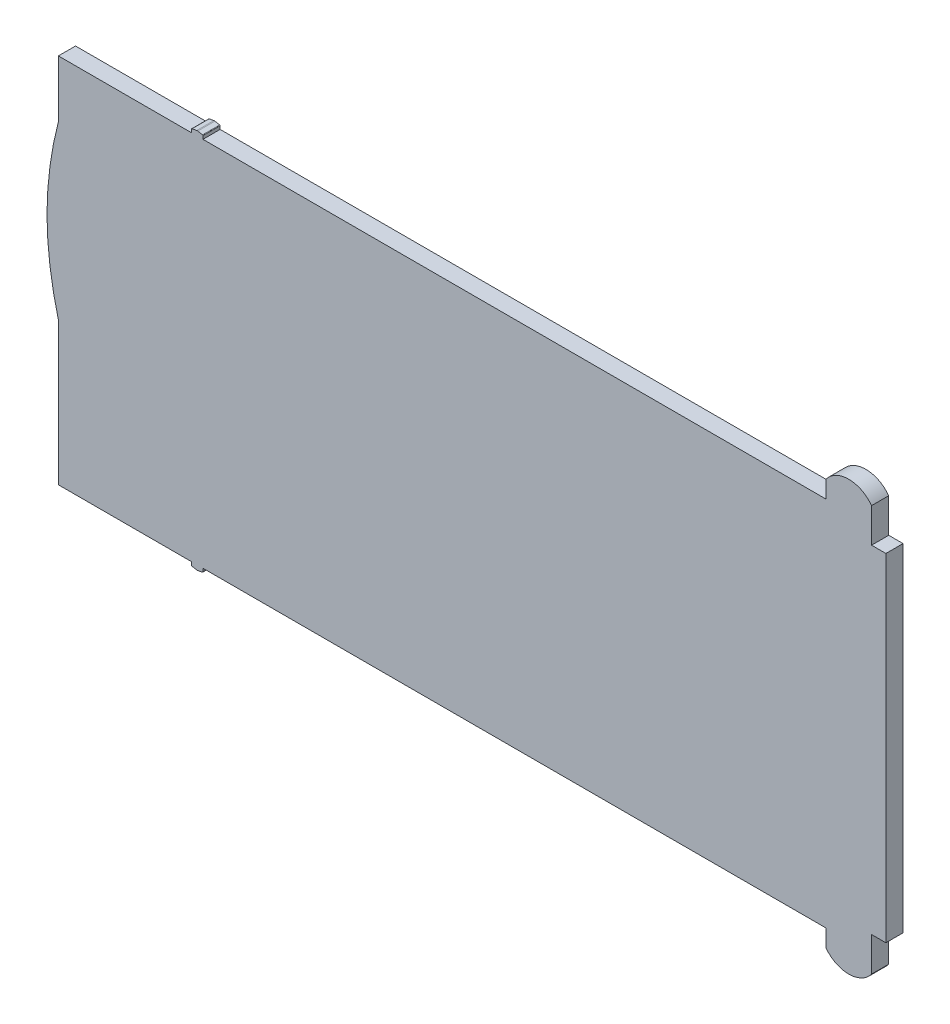
SolidWorks part; units mm, degrees
material "Vidrio"
ref_plane "Alzado" through (0, 0, 0) normal (0, 0, 1) x (1, 0, 0)
ref_plane "Planta" through (0, 0, 0) normal (0, 1, 0) x (1, 0, 0)
ref_plane "Vista lateral" through (0, 0, 0) normal (1, 0, 0) x (0, 0, -1)
sketch "Croquis1" plane through (0, 0, 0) normal (0, 0, 1) x (1, 0, 0)
  line L0 (23.1977, 55.1953) -> (17.6238, 55.1517)
  line L1 (17.6238, 55.1517) -> (19.2257, 49.2985)
  line L2 (21.9668, 38.9626) -> (21.0109, 39.0194)
  line L3 (21.0109, 39.0194) -> (18.7543, 47.2339)
  line L4 (35.1267, 52.7205) -> (35.7465, 50.9877)
  line L5 (35.7465, 50.9877) -> (33.2105, 49.6869)
  line L6 (27.676, 46.9939) -> (26.707, 46.4745)
  line L7 (26.707, 46.4745) -> (27.0387, 46.1034)
  line L8 (29.3302, 43.6068) -> (31.2289, 41.5466)
  line L9 (31.2289, 41.5466) -> (32.0146, 39.1983)
  line L10 (30.4913, 38.7484) -> (28.3743, 40.857)
  line L11 (28.3743, 40.857) -> (27.7982, 40.5165)
  line L12 (27.7982, 40.5165) -> (27.0867, 40.0975)
  line L13 (27.0867, 40.0975) -> (26.4626, 41.1014)
  line L14 (24.817, 43.7639) -> (23.7302, 45.5273)
  line L15 (23.7302, 45.5273) -> (24.0576, 47.2514)
  line L16 (33.6427, 44.4885) -> (31.2158, 42.7862)
  line L17 (31.2158, 42.7862) -> (29.5397, 44.4448)
  line L18 (155.5622, 17.217) -> (155.5622, 76.2168)
  line L19 (153.0622, 82.2168) -> (153.0622, 79.2168)
  line L20 (145.0622, 82.2168) -> (145.0622, 79.2168)
  line L21 (145.0622, 11.217) -> (145.0622, 14.217)
  line L22 (153.0622, 11.217) -> (153.0622, 14.217)
  line L23 (34.0621, 79.2168) -> (10.0621, 79.2168)
  line L24 (10.0621, 14.217) -> (10.0621, 79.2168)
  line L25 (10.0621, 79.2168) -> (34.0621, 79.2168)
  line L27 (145.0622, 79.2168) -> (36.0621, 79.2252)
  line L28 (10.0621, 14.217) -> (34.0437, 14.217)
  line L29 (36.0437, 14.2253) -> (145.0622, 14.217)
  line L30 (34.1437, 79.8689) -> (34.97, 80.0238)
  line L31 (35.9805, 79.8689) -> (35.1543, 80.0238)
  line L32 (35.9621, 13.5732) -> (35.1358, 13.4183)
  line L33 (34.1253, 13.5732) -> (34.9515, 13.4183)
  line L34 (153.0622, 14.217) -> (153.0622, 17.217)
  line L35 (153.0622, 17.217) -> (155.5622, 17.217)
  line L36 (153.0622, 79.2168) -> (153.0622, 76.2168)
  line L37 (153.0622, 76.2168) -> (155.5622, 76.2168)
  line L38 (36.0621, 79.2252) -> (36.0621, 79.7706)
  line L39 (34.0621, 79.7706) -> (34.0621, 79.2168)
  line L40 (34.0437, 14.217) -> (34.0437, 13.6715)
  line L41 (36.0437, 13.6715) -> (36.0437, 14.2253)
  arc A1 (34.1437, 79.8689) -> (34.0621, 79.7706) centre (34.1621, 79.7706) ccw
  arc A2 (36.0621, 79.7706) -> (35.9805, 79.8689) centre (35.9621, 79.7706) ccw
  arc A3 (35.9621, 13.5732) -> (36.0437, 13.6715) centre (35.9437, 13.6715) ccw
  arc A4 (34.0437, 13.6715) -> (34.1253, 13.5732) centre (34.1437, 13.6715) ccw
  arc A5 (35.1543, 80.0238) -> (34.97, 80.0238) centre (35.0621, 79.5324) ccw
  arc A6 (34.9515, 13.4183) -> (35.1358, 13.4183) centre (35.0437, 13.9097) ccw
  arc A7 (153.0622, 82.2168) -> (145.0622, 82.2168) centre (149.0622, 79.2165) ccw
  arc A8 (145.0622, 11.217) -> (153.0622, 11.217) centre (149.0622, 14.217) ccw
  spline S0 degree 3 poles (22.9882, 56.2909) (24.465, 56.2802) (25.9512, 56.2546) (27.1129, 56.2211) knots 0 0 0 0 1 1 1 1
  spline S1 degree 3 poles (27.1129, 56.2211) (27.6938, 56.2043) (28.1916, 56.1859) (28.5708, 56.1643) knots 0 0 0 0 1 1 1 1
  spline S2 degree 3 poles (28.5708, 56.1643) (28.9499, 56.1427) (29.1978, 56.1233) (29.3171, 56.0901) knots 0 0 0 0 1 1 1 1
  spline S3 degree 3 poles (29.3171, 56.0901) (30.1079, 55.8706) (30.8888, 55.1338) (31.4122, 54.318) knots 0 0 0 0 1 1 1 1
  spline S4 degree 3 poles (31.4122, 54.318) (31.674, 53.9101) (31.8707, 53.4822) (31.9666, 53.0828) knots 0 0 0 0 1 1 1 1
  spline S5 degree 3 poles (31.9666, 53.0828) (32.0625, 52.6834) (32.0614, 52.3092) (31.9055, 52.0178) knots 0 0 0 0 1 1 1 1
  spline S6 degree 3 poles (31.9055, 52.0178) (31.8337, 51.8836) (31.7742, 51.787) (31.696, 51.7253) knots 0 0 0 0 1 1 1 1
  spline S7 degree 3 poles (31.696, 51.7253) (31.6568, 51.6945) (31.6061, 51.6722) (31.5519, 51.6773) knots 0 0 0 0 1 1 1 1
  spline S8 degree 3 poles (31.5519, 51.6773) (31.4977, 51.6824) (31.449, 51.7134) (31.4122, 51.7515) knots 0 0 0 0 1 1 1 1
  spline S9 degree 3 poles (31.4122, 51.7515) (31.3388, 51.8278) (31.2827, 51.9445) (31.2115, 52.1225) knots 0 0 0 0 1 1 1 1
  spline S10 degree 3 poles (31.2115, 52.1225) (31.1403, 52.3005) (31.0608, 52.5367) (30.9627, 52.8427) knots 0 0 0 0 1 1 1 1
  spline S11 degree 3 poles (30.9627, 52.8427) (30.5664, 54.0785) (30.176, 54.6186) (29.4481, 54.964) knots 0 0 0 0 1 1 1 1
  spline S12 degree 3 poles (29.4481, 54.964) (29.198, 55.0826) (28.8811, 55.1528) (27.999, 55.1866) knots 0 0 0 0 1 1 1 1
  spline S13 degree 3 poles (27.999, 55.1866) (27.1169, 55.2204) (25.6803, 55.2155) (23.1977, 55.1953) knots 0 0 0 0 1 1 1 1
  spline S14 degree 3 poles (19.2257, 49.2985) (20.1234, 46.0188) (21.0684, 42.5658) (21.3252, 41.6252) knots 0 0 0 0 1 1 1 1
  spline S15 degree 3 poles (21.3252, 41.6252) (21.5575, 40.7742) (21.6788, 40.3445) (21.7922, 40.1542) knots 0 0 0 0 1 1 1 1
  spline S16 degree 3 poles (21.7922, 40.1542) (21.8489, 40.0591) (21.8933, 40.0262) (21.9581, 40.0058) knots 0 0 0 0 1 1 1 1
  spline S17 degree 3 poles (21.9581, 40.0058) (22.0229, 39.9855) (22.1186, 39.9826) (22.2549, 39.984) knots 0 0 0 0 1 1 1 1
  spline S18 degree 3 poles (22.2549, 39.984) (22.5346, 39.9868) (22.9349, 40.1132) (23.0929, 40.2328) knots 0 0 0 0 1 1 1 1
  spline S19 degree 3 poles (23.0929, 40.2328) (23.567, 40.5914) (24.1358, 40.577) (24.5595, 40.1935) knots 0 0 0 0 1 1 1 1
  spline S20 degree 3 poles (24.5595, 40.1935) (24.9472, 39.8426) (25.0001, 39.3177) (24.7166, 38.788) knots 0 0 0 0 1 1 1 1
  spline S21 degree 3 poles (24.7166, 38.788) (24.5805, 38.5338) (24.2425, 38.4181) (23.9004, 38.3996) knots 0 0 0 0 1 1 1 1
  spline S22 degree 3 poles (23.9004, 38.3996) (23.5584, 38.381) (23.1997, 38.4591) (23.01, 38.6877) knots 0 0 0 0 1 1 1 1
  spline S23 degree 3 poles (23.01, 38.6877) (22.9777, 38.7266) (22.8378, 38.8007) (22.6477, 38.8535) knots 0 0 0 0 1 1 1 1
  spline S24 degree 3 poles (22.6477, 38.8535) (22.4576, 38.9063) (22.2156, 38.948) (21.9668, 38.9626) knots 0 0 0 0 1 1 1 1
  spline S25 degree 3 poles (18.7543, 47.2339) (18.1386, 49.4769) (17.5776, 51.5477) (17.1699, 53.0784) knots 0 0 0 0 1 1 1 1
  spline S26 degree 3 poles (17.1699, 53.0784) (16.966, 53.8438) (16.8004, 54.4756) (16.6854, 54.9247) knots 0 0 0 0 1 1 1 1
  spline S27 degree 3 poles (16.6854, 54.9247) (16.6279, 55.1493) (16.5809, 55.3286) (16.5501, 55.4572) knots 0 0 0 0 1 1 1 1
  spline S28 degree 3 poles (16.5501, 55.4572) (16.5347, 55.5216) (16.5235, 55.5711) (16.5152, 55.61) knots 0 0 0 0 1 1 1 1
  spline S29 degree 3 poles (16.5152, 55.61) (16.5069, 55.6489) (16.5032, 55.6672) (16.5021, 55.6973) knots 0 0 0 0 1 1 1 1
  spline S30 degree 3 poles (16.5021, 55.6973) (16.4949, 55.9024) (16.6315, 56.1032) (16.8251, 56.1774) knots 0 0 0 0 1 1 1 1
  spline S31 degree 3 poles (16.8251, 56.1774) (16.8825, 56.1995) (16.9526, 56.2063) (17.0651, 56.2167) knots 0 0 0 0 1 1 1 1
  spline S32 degree 3 poles (17.0651, 56.2167) (17.1777, 56.2271) (17.3227, 56.2391) (17.5016, 56.2473) knots 0 0 0 0 1 1 1 1
  spline S33 degree 3 poles (17.5016, 56.2473) (17.8595, 56.2636) (18.3449, 56.2737) (18.9115, 56.2822) knots 0 0 0 0 1 1 1 1
  spline S34 degree 3 poles (18.9115, 56.2822) (20.0446, 56.2991) (21.5114, 56.3016) (22.9882, 56.2909) knots 0 0 0 0 1 1 1 1
  spline S35 degree 3 poles (34.4109, 54.4926) (34.4112, 54.4925) (34.4543, 54.471) (34.4545, 54.4708) knots 0 0 0 0 1 1 1 1
  spline S36 degree 3 poles (34.4545, 54.4708) (34.455, 54.4703) (34.4652, 54.461) (34.4676, 54.4577) knots 0 0 0 0 1 1 1 1
  spline S37 degree 3 poles (34.4676, 54.4577) (34.47, 54.4544) (34.4704, 54.4515) (34.472, 54.4489) knots 0 0 0 0 1 1 1 1
  spline S38 degree 3 poles (34.472, 54.4489) (34.4751, 54.4438) (34.4782, 54.4365) (34.4807, 54.4315) knots 0 0 0 0 1 1 1 1
  spline S39 degree 3 poles (34.4807, 54.4315) (34.4858, 54.4216) (34.4921, 54.4103) (34.4982, 54.3966) knots 0 0 0 0 1 1 1 1
  spline S40 degree 3 poles (34.4982, 54.3966) (34.5104, 54.3691) (34.5232, 54.3334) (34.5418, 54.2875) knots 0 0 0 0 1 1 1 1
  spline S41 degree 3 poles (34.5418, 54.2875) (34.5789, 54.1955) (34.6312, 54.0679) (34.6902, 53.9121) knots 0 0 0 0 1 1 1 1
  spline S42 degree 3 poles (34.6902, 53.9121) (34.8083, 53.6004) (34.9626, 53.1779) (35.1267, 52.7205) knots 0 0 0 0 1 1 1 1
  spline S43 degree 3 poles (33.2105, 49.6869) (32.5306, 49.3396) (31.8967, 49.0229) (31.4253, 48.7922) knots 0 0 0 0 1 1 1 1
  spline S44 degree 3 poles (31.4253, 48.7922) (31.1897, 48.6768) (30.9951, 48.5828) (30.8536, 48.5172) knots 0 0 0 0 1 1 1 1
  spline S45 degree 3 poles (30.8536, 48.5172) (30.7828, 48.4843) (30.7262, 48.4611) (30.6833, 48.443) knots 0 0 0 0 1 1 1 1
  spline S46 degree 3 poles (30.6833, 48.443) (30.6619, 48.4339) (30.6416, 48.4267) (30.6266, 48.4211) knots 0 0 0 0 1 1 1 1
  spline S47 degree 3 poles (30.6266, 48.4211) (30.6191, 48.4184) (30.6119, 48.4145) (30.6047, 48.4124) knots 0 0 0 0 1 1 1 1
  spline S48 degree 3 poles (30.6047, 48.4124) (30.5976, 48.4103) (30.5807, 48.4082) (30.5786, 48.408) knots 0 0 0 0 1 1 1 1
  spline S49 degree 3 poles (30.5786, 48.408) (30.578, 48.408) (30.5484, 48.4123) (30.548, 48.4124) knots 0 0 0 0 1 1 1 1
  spline S50 degree 3 poles (30.548, 48.4124) (30.5476, 48.4125) (30.5134, 48.4296) (30.5131, 48.4299) knots 0 0 0 0 1 1 1 1
  spline S51 degree 3 poles (30.5131, 48.4299) (30.5128, 48.4301) (30.4915, 48.46) (30.4913, 48.4604) knots 0 0 0 0 1 1 1 1
  spline S52 degree 3 poles (30.4913, 48.4604) (30.491, 48.4609) (30.4826, 48.4816) (30.4825, 48.4822) knots 0 0 0 0 1 1 1 1
  spline S53 degree 3 poles (30.4825, 48.4822) (30.4824, 48.4828) (30.4782, 48.4989) (30.4782, 48.4997) knots 0 0 0 0 1 1 1 1
  spline S54 degree 3 poles (30.4782, 48.4997) (30.4782, 48.5005) (30.4821, 48.5091) (30.4825, 48.5128) knots 0 0 0 0 1 1 1 1
  spline S55 degree 3 poles (30.4825, 48.5128) (30.4833, 48.5201) (30.4812, 48.525) (30.4825, 48.5302) knots 0 0 0 0 1 1 1 1
  spline S56 degree 3 poles (30.4825, 48.5302) (30.4877, 48.5514) (30.4944, 48.5694) (30.5043, 48.5913) knots 0 0 0 0 1 1 1 1
  spline S57 degree 3 poles (30.5043, 48.5913) (30.5243, 48.6352) (30.5579, 48.694) (30.6004, 48.7703) knots 0 0 0 0 1 1 1 1
  spline S58 degree 3 poles (30.6004, 48.7703) (30.6854, 48.923) (30.8147, 49.1415) (30.9801, 49.412) knots 0 0 0 0 1 1 1 1
  spline S59 degree 3 poles (30.9801, 49.412) (31.3109, 49.9529) (31.7843, 50.6981) (32.3201, 51.5202) knots 0 0 0 0 1 1 1 1
  spline S60 degree 3 poles (32.3201, 51.5202) (32.8559, 52.3421) (33.3493, 53.0828) (33.7125, 53.6153) knots 0 0 0 0 1 1 1 1
  spline S61 degree 3 poles (33.7125, 53.6153) (33.8941, 53.8815) (34.0427, 54.0973) (34.149, 54.2438) knots 0 0 0 0 1 1 1 1
  spline S62 degree 3 poles (34.149, 54.2438) (34.2021, 54.3171) (34.244, 54.3708) (34.2756, 54.4097) knots 0 0 0 0 1 1 1 1
  spline S63 degree 3 poles (34.2756, 54.4097) (34.2913, 54.4291) (34.3019, 54.4448) (34.3148, 54.4577) knots 0 0 0 0 1 1 1 1
  spline S64 degree 3 poles (34.3148, 54.4577) (34.3213, 54.4641) (34.3284, 54.4714) (34.341, 54.4795) knots 0 0 0 0 1 1 1 1
  spline S65 degree 3 poles (34.341, 54.4795) (34.3442, 54.4815) (34.3536, 54.4836) (34.3541, 54.4839) knots 0 0 0 0 1 1 1 1
  spline S66 degree 3 poles (34.3541, 54.4839) (34.3547, 54.4841) (34.3711, 54.4925) (34.3716, 54.4926) knots 0 0 0 0 1 1 1 1
  spline S67 degree 3 poles (34.3716, 54.4926) (34.372, 54.4927) (34.4105, 54.4927) (34.4109, 54.4926) knots 0 0 0 0 1 1 1 1
  spline S68 degree 3 poles (20.2078, 53.445) (20.241, 53.4449) (20.2808, 53.4417) (20.33, 53.4363) knots 0 0 0 0 1 1 1 1
  spline S69 degree 3 poles (20.33, 53.4363) (20.4284, 53.4256) (20.562, 53.4079) (20.7228, 53.3796) knots 0 0 0 0 1 1 1 1
  spline S70 degree 3 poles (20.7228, 53.3796) (21.0446, 53.3229) (21.4762, 53.2337) (21.9406, 53.1264) knots 0 0 0 0 1 1 1 1
  spline S71 degree 3 poles (21.9406, 53.1264) (22.7572, 52.9377) (23.1816, 52.8405) (23.5076, 52.8296) knots 0 0 0 0 1 1 1 1
  spline S72 degree 3 poles (23.5076, 52.8296) (23.8336, 52.8187) (24.0705, 52.8892) (24.5333, 53.0348) knots 0 0 0 0 1 1 1 1
  spline S73 degree 3 poles (24.5333, 53.0348) (25.5486, 53.3541) (26.2772, 53.3011) (27.1827, 52.8383) knots 0 0 0 0 1 1 1 1
  spline S74 degree 3 poles (27.1827, 52.8383) (27.5743, 52.6383) (27.8631, 52.3158) (28.0601, 51.8301) knots 0 0 0 0 1 1 1 1
  spline S75 degree 3 poles (28.0601, 51.8301) (28.257, 51.3443) (28.3695, 50.6957) (28.4311, 49.8092) knots 0 0 0 0 1 1 1 1
  spline S76 degree 3 poles (28.4311, 49.8092) (28.4611, 49.3767) (28.502, 48.9498) (28.5446, 48.6132) knots 0 0 0 0 1 1 1 1
  spline S77 degree 3 poles (28.5446, 48.6132) (28.5658, 48.4449) (28.5854, 48.2979) (28.6057, 48.1855) knots 0 0 0 0 1 1 1 1
  spline S78 degree 3 poles (28.6057, 48.1855) (28.626, 48.073) (28.6487, 47.9887) (28.6581, 47.9672) knots 0 0 0 0 1 1 1 1
  spline S79 degree 3 poles (28.6581, 47.9672) (28.689, 47.8962) (28.7008, 47.8176) (28.6755, 47.7402) knots 0 0 0 0 1 1 1 1
  spline S80 degree 3 poles (28.6755, 47.7402) (28.6503, 47.6629) (28.5967, 47.5935) (28.5184, 47.522) knots 0 0 0 0 1 1 1 1
  spline S81 degree 3 poles (28.5184, 47.522) (28.3616, 47.3791) (28.0966, 47.2181) (27.676, 46.9939) knots 0 0 0 0 1 1 1 1
  spline S82 degree 3 poles (27.0387, 46.1034) (27.263, 45.855) (28.2947, 44.7315) (29.3302, 43.6068) knots 0 0 0 0 1 1 1 1
  spline S83 degree 3 poles (32.0146, 39.1983) (32.2298, 38.5567) (32.427, 37.9622) (32.5689, 37.5223) knots 0 0 0 0 1 1 1 1
  spline S84 degree 3 poles (32.5689, 37.5223) (32.6399, 37.3023) (32.6948, 37.12) (32.7348, 36.9898) knots 0 0 0 0 1 1 1 1
  spline S85 degree 3 poles (32.7348, 36.9898) (32.7548, 36.9247) (32.772, 36.8754) (32.7828, 36.837) knots 0 0 0 0 1 1 1 1
  spline S86 degree 3 poles (32.7828, 36.837) (32.7882, 36.8178) (32.7928, 36.8019) (32.7959, 36.789) knots 0 0 0 0 1 1 1 1
  spline S87 degree 3 poles (32.7959, 36.789) (32.7974, 36.7825) (32.7992, 36.7731) (32.8002, 36.7671) knots 0 0 0 0 1 1 1 1
  spline S88 degree 3 poles (32.8002, 36.7671) (32.8014, 36.7613) (32.8002, 36.7467) (32.8002, 36.7452) knots 0 0 0 0 1 1 1 1
  spline S89 degree 3 poles (32.8002, 36.7452) (32.8002, 36.7448) (32.796, 36.7105) (32.7959, 36.7102) knots 0 0 0 0 1 1 1 1
  spline S90 degree 3 poles (32.7959, 36.7102) (32.7958, 36.71) (32.7612, 36.6711) (32.761, 36.671) knots 0 0 0 0 1 1 1 1
  spline S91 degree 3 poles (32.761, 36.671) (32.7607, 36.6708) (32.722, 36.658) (32.7217, 36.6578) knots 0 0 0 0 1 1 1 1
  spline S92 degree 3 poles (32.7217, 36.6578) (32.7213, 36.6577) (32.7003, 36.6577) (32.6999, 36.6578) knots 0 0 0 0 1 1 1 1
  spline S93 degree 3 poles (32.6999, 36.6578) (32.6989, 36.6579) (32.6792, 36.6597) (32.6737, 36.662) knots 0 0 0 0 1 1 1 1
  spline S94 degree 3 poles (32.6737, 36.662) (32.6681, 36.6645) (32.6644, 36.6685) (32.6606, 36.6707) knots 0 0 0 0 1 1 1 1
  spline S95 degree 3 poles (32.6606, 36.6707) (32.6452, 36.6797) (32.6329, 36.6886) (32.6169, 36.7013) knots 0 0 0 0 1 1 1 1
  spline S96 degree 3 poles (32.6169, 36.7013) (32.585, 36.7265) (32.5415, 36.7649) (32.486, 36.8148) knots 0 0 0 0 1 1 1 1
  spline S97 degree 3 poles (32.486, 36.8148) (32.3748, 36.9145) (32.2153, 37.0638) (32.019, 37.2513) knots 0 0 0 0 1 1 1 1
  spline S98 degree 3 poles (32.019, 37.2513) (31.6263, 37.6262) (31.0864, 38.1547) (30.4913, 38.7484) knots 0 0 0 0 1 1 1 1
  spline S99 degree 3 poles (26.4626, 41.1014) (26.1453, 41.6137) (25.4049, 42.8113) (24.817, 43.7639) knots 0 0 0 0 1 1 1 1
  spline S100 degree 3 poles (24.0576, 47.2514) (24.2337, 48.1791) (24.4293, 49.4157) (24.4897, 49.9881) knots 0 0 0 0 1 1 1 1
  spline S101 degree 3 poles (24.4897, 49.9881) (24.5411, 50.4762) (24.5583, 50.7412) (24.5159, 50.9222) knots 0 0 0 0 1 1 1 1
  spline S102 degree 3 poles (24.5159, 50.9222) (24.4734, 51.1032) (24.373, 51.2182) (24.1579, 51.4329) knots 0 0 0 0 1 1 1 1
  spline S103 degree 3 poles (24.1579, 51.4329) (24.0335, 51.5571) (23.7396, 51.7414) (23.3417, 51.9348) knots 0 0 0 0 1 1 1 1
  spline S104 degree 3 poles (23.3417, 51.9348) (22.9439, 52.1283) (22.4427, 52.3353) (21.8882, 52.5328) knots 0 0 0 0 1 1 1 1
  spline S105 degree 3 poles (21.8882, 52.5328) (21.3815, 52.7134) (20.9305, 52.8878) (20.6094, 53.0217) knots 0 0 0 0 1 1 1 1
  spline S106 degree 3 poles (20.6094, 53.0217) (20.4488, 53.0886) (20.3174, 53.1429) (20.2296, 53.1875) knots 0 0 0 0 1 1 1 1
  spline S107 degree 3 poles (20.2296, 53.1875) (20.1857, 53.2098) (20.1559, 53.2296) (20.1292, 53.2486) knots 0 0 0 0 1 1 1 1
  spline S108 degree 3 poles (20.1292, 53.2486) (20.1159, 53.2581) (20.1043, 53.2645) (20.0899, 53.2836) knots 0 0 0 0 1 1 1 1
  spline S109 degree 3 poles (20.0899, 53.2836) (20.0864, 53.2883) (20.0774, 53.3043) (20.0769, 53.3054) knots 0 0 0 0 1 1 1 1
  spline S110 degree 3 poles (20.0769, 53.3054) (20.0763, 53.3065) (20.0682, 53.3306) (20.0681, 53.3316) knots 0 0 0 0 1 1 1 1
  spline S111 degree 3 poles (20.0681, 53.3316) (20.068, 53.3325) (20.0722, 53.3744) (20.0725, 53.3752) knots 0 0 0 0 1 1 1 1
  spline S112 degree 3 poles (20.0725, 53.3752) (20.0728, 53.376) (20.0936, 53.4095) (20.0943, 53.4101) knots 0 0 0 0 1 1 1 1
  spline S113 degree 3 poles (20.0943, 53.4101) (20.095, 53.4108) (20.1151, 53.427) (20.1161, 53.4276) knots 0 0 0 0 1 1 1 1
  spline S114 degree 3 poles (20.1161, 53.4276) (20.1172, 53.4282) (20.1285, 53.4345) (20.1336, 53.4363) knots 0 0 0 0 1 1 1 1
  spline S115 degree 3 poles (20.1336, 53.4363) (20.1439, 53.44) (20.1518, 53.4395) (20.1598, 53.4407) knots 0 0 0 0 1 1 1 1
  spline S116 degree 3 poles (20.1598, 53.4407) (20.1757, 53.4431) (20.1912, 53.4451) (20.2078, 53.445) knots 0 0 0 0 1 1 1 1
  spline S117 degree 3 poles (37.9158, 51.1492) (37.9167, 51.1491) (37.9413, 51.145) (37.942, 51.1448) knots 0 0 0 0 1 1 1 1
  spline S118 degree 3 poles (37.942, 51.1448) (37.9426, 51.1446) (37.9766, 51.1233) (37.9769, 51.123) knots 0 0 0 0 1 1 1 1
  spline S119 degree 3 poles (37.9769, 51.123) (37.9779, 51.122) (37.9935, 51.0983) (37.9944, 51.0968) knots 0 0 0 0 1 1 1 1
  spline S120 degree 3 poles (37.9944, 51.0968) (37.9952, 51.0953) (38.0011, 51.0857) (38.0031, 51.0793) knots 0 0 0 0 1 1 1 1
  spline S121 degree 3 poles (38.0031, 51.0793) (38.0072, 51.0666) (38.0109, 51.0548) (38.0118, 51.0444) knots 0 0 0 0 1 1 1 1
  spline S122 degree 3 poles (38.0118, 51.0444) (38.0136, 51.0237) (38.0098, 51.0053) (38.0075, 50.9833) knots 0 0 0 0 1 1 1 1
  spline S123 degree 3 poles (38.0075, 50.9833) (38.0029, 50.9393) (37.9963, 50.8823) (37.9813, 50.8174) knots 0 0 0 0 1 1 1 1
  spline S124 degree 3 poles (37.9813, 50.8174) (37.9512, 50.6878) (37.9013, 50.5168) (37.8373, 50.3111) knots 0 0 0 0 1 1 1 1
  spline S125 degree 3 poles (37.8373, 50.3111) (37.7093, 49.8998) (37.5207, 49.3604) (37.3222, 48.8184) knots 0 0 0 0 1 1 1 1
  spline S126 degree 3 poles (37.3222, 48.8184) (37.1237, 48.2763) (36.9132, 47.73) (36.733, 47.2994) knots 0 0 0 0 1 1 1 1
  spline S127 degree 3 poles (36.733, 47.2994) (36.6428, 47.0841) (36.5624, 46.8968) (36.4929, 46.7538) knots 0 0 0 0 1 1 1 1
  spline S128 degree 3 poles (36.4929, 46.7538) (36.4234, 46.6109) (36.3771, 46.5208) (36.3183, 46.4614) knots 0 0 0 0 1 1 1 1
  spline S129 degree 3 poles (36.3183, 46.4614) (36.2674, 46.4099) (36.1648, 46.3245) (36.0084, 46.2039) knots 0 0 0 0 1 1 1 1
  spline S130 degree 3 poles (36.0084, 46.2039) (35.852, 46.0832) (35.6434, 45.9321) (35.4017, 45.7543) knots 0 0 0 0 1 1 1 1
  spline S131 degree 3 poles (35.4017, 45.7543) (34.9184, 45.3986) (34.2943, 44.9458) (33.6427, 44.4885) knots 0 0 0 0 1 1 1 1
  spline S132 degree 3 poles (29.5397, 44.4448) (29.093, 44.8869) (28.6868, 45.2991) (28.3918, 45.6102) knots 0 0 0 0 1 1 1 1
  spline S133 degree 3 poles (28.3918, 45.6102) (28.2443, 45.7658) (28.1264, 45.8942) (28.0426, 45.99) knots 0 0 0 0 1 1 1 1
  spline S134 degree 3 poles (28.0426, 45.99) (28.0007, 46.0379) (27.966, 46.0767) (27.9422, 46.1078) knots 0 0 0 0 1 1 1 1
  spline S135 degree 3 poles (27.9422, 46.1078) (27.9303, 46.1234) (27.9199, 46.1381) (27.9117, 46.1515) knots 0 0 0 0 1 1 1 1
  spline S136 degree 3 poles (27.9117, 46.1515) (27.9075, 46.1582) (27.9068, 46.1645) (27.9029, 46.1733) knots 0 0 0 0 1 1 1 1
  spline S137 degree 3 poles (27.9029, 46.1733) (27.901, 46.1777) (27.8946, 46.1895) (27.8942, 46.1908) knots 0 0 0 0 1 1 1 1
  spline S138 degree 3 poles (27.8942, 46.1908) (27.8938, 46.192) (27.8898, 46.216) (27.8898, 46.2169) knots 0 0 0 0 1 1 1 1
  spline S139 degree 3 poles (27.8898, 46.2169) (27.8898, 46.2175) (27.8983, 46.2556) (27.8986, 46.2562) knots 0 0 0 0 1 1 1 1
  spline S140 degree 3 poles (27.8986, 46.2562) (27.8989, 46.2569) (27.9111, 46.2729) (27.9117, 46.2737) knots 0 0 0 0 1 1 1 1
  spline S141 degree 3 poles (27.9117, 46.2737) (27.9129, 46.2753) (27.9242, 46.2867) (27.9291, 46.2911) knots 0 0 0 0 1 1 1 1
  spline S142 degree 3 poles (27.9291, 46.2911) (27.9389, 46.3001) (27.9443, 46.3053) (27.9553, 46.313) knots 0 0 0 0 1 1 1 1
  spline S143 degree 3 poles (27.9553, 46.313) (27.9774, 46.3284) (28.0099, 46.3479) (28.047, 46.3697) knots 0 0 0 0 1 1 1 1
  spline S144 degree 3 poles (28.047, 46.3697) (28.1211, 46.4133) (28.226, 46.4721) (28.3612, 46.5443) knots 0 0 0 0 1 1 1 1
  spline S145 degree 3 poles (28.3612, 46.5443) (28.6318, 46.6886) (29.016, 46.8867) (29.4786, 47.1205) knots 0 0 0 0 1 1 1 1
  spline S146 degree 3 poles (29.4786, 47.1205) (30.4039, 47.588) (31.6376, 48.1981) (32.8745, 48.8009) knots 0 0 0 0 1 1 1 1
  spline S147 degree 3 poles (32.8745, 48.8009) (34.1113, 49.4037) (35.3513, 49.9979) (36.2877, 50.4377) knots 0 0 0 0 1 1 1 1
  spline S148 degree 3 poles (36.2877, 50.4377) (36.7559, 50.6576) (37.148, 50.838) (37.4269, 50.9615) knots 0 0 0 0 1 1 1 1
  spline S149 degree 3 poles (37.4269, 50.9615) (37.5664, 51.0232) (37.6794, 51.0743) (37.7587, 51.1055) knots 0 0 0 0 1 1 1 1
  spline S150 degree 3 poles (37.7587, 51.1055) (37.7983, 51.1211) (37.8292, 51.1327) (37.8547, 51.1404) knots 0 0 0 0 1 1 1 1
  spline S151 degree 3 poles (37.8547, 51.1404) (37.8674, 51.1443) (37.8762, 51.1471) (37.8896, 51.1492) knots 0 0 0 0 1 1 1 1
  spline S152 degree 3 poles (37.8896, 51.1492) (37.8963, 51.1502) (37.9139, 51.1493) (37.9158, 51.1492) knots 0 0 0 0 1 1 1 1
  spline S153 degree 3 poles (34.6422, 44.3663) (34.6433, 44.3663) (34.6758, 44.3581) (34.6771, 44.3575) knots 0 0 0 0 1 1 1 1
  spline S154 degree 3 poles (34.6771, 44.3575) (34.6784, 44.357) (34.6932, 44.3485) (34.699, 44.3444) knots 0 0 0 0 1 1 1 1
  spline S155 degree 3 poles (34.699, 44.3444) (34.7104, 44.3363) (34.7186, 44.33) (34.7251, 44.3226) knots 0 0 0 0 1 1 1 1
  spline S156 degree 3 poles (34.7251, 44.3226) (34.7382, 44.3077) (34.7487, 44.2932) (34.7601, 44.2746) knots 0 0 0 0 1 1 1 1
  spline S157 degree 3 poles (34.7601, 44.2746) (34.7828, 44.2375) (34.8087, 44.1889) (34.8386, 44.1262) knots 0 0 0 0 1 1 1 1
  spline S158 degree 3 poles (34.8386, 44.1262) (34.8984, 44.0007) (34.9728, 43.8219) (35.0612, 43.6024) knots 0 0 0 0 1 1 1 1
  spline S159 degree 3 poles (35.0612, 43.6024) (35.2382, 43.1634) (35.4668, 42.5601) (35.6985, 41.8958) knots 0 0 0 0 1 1 1 1
  spline S160 degree 3 poles (35.6985, 41.8958) (36.161, 40.5694) (36.5732, 39.382) (36.6151, 39.2638) knots 0 0 0 0 1 1 1 1
  spline S161 degree 3 poles (36.6151, 39.2638) (36.6325, 39.2148) (36.6378, 39.16) (36.6194, 39.111) knots 0 0 0 0 1 1 1 1
  spline S162 degree 3 poles (36.6194, 39.111) (36.6011, 39.0621) (36.5626, 39.0238) (36.5191, 38.9976) knots 0 0 0 0 1 1 1 1
  spline S163 degree 3 poles (36.5191, 38.9976) (36.432, 38.9452) (36.3174, 38.9277) (36.1699, 38.9277) knots 0 0 0 0 1 1 1 1
  spline S164 degree 3 poles (36.1699, 38.9277) (36.0611, 38.9277) (35.9568, 38.9391) (35.86, 39.0019) knots 0 0 0 0 1 1 1 1
  spline S165 degree 3 poles (35.86, 39.0019) (35.7632, 39.0647) (35.6802, 39.1713) (35.5937, 39.338) knots 0 0 0 0 1 1 1 1
  spline S166 degree 3 poles (35.5937, 39.338) (35.4208, 39.6714) (35.2163, 40.2682) (34.843, 41.3851) knots 0 0 0 0 1 1 1 1
  spline S167 degree 3 poles (34.843, 41.3851) (34.5414, 42.2875) (34.35, 42.9022) (34.2537, 43.3187) knots 0 0 0 0 1 1 1 1
  spline S168 degree 3 poles (34.2537, 43.3187) (34.2056, 43.527) (34.1829, 43.6834) (34.1795, 43.8076) knots 0 0 0 0 1 1 1 1
  spline S169 degree 3 poles (34.1795, 43.8076) (34.1762, 43.9318) (34.1911, 44.0299) (34.2494, 44.1) knots 0 0 0 0 1 1 1 1
  spline S170 degree 3 poles (34.2494, 44.1) (34.3077, 44.1703) (34.3757, 44.2317) (34.4414, 44.279) knots 0 0 0 0 1 1 1 1
  spline S171 degree 3 poles (34.4414, 44.279) (34.5071, 44.3262) (34.5636, 44.3663) (34.6422, 44.3663) knots 0 0 0 0 1 1 1 1
extrude "Saliente-Extruir1" add sketch "Croquis1" along normal blind 3
sketch "Croquis4" plane through (0.0061, 79.2279, 0) normal (0.0001, 1, 0) x (1, -0.0001, 0)
  line L0 (145.0561, -3) -> (153.0559, 0) construction
  circle A0 centre (149.056, -1.5) radius 7.5641 construction
sketch "Croquis8" plane through (10.0621, 0, 0) normal (-1, 0, 0) x (0, 0, 1)
  line L4 (0, 79.2168) -> (0, 14.217)
  line L5 (0, 14.217) -> (3, 14.217)
  line L6 (3, 14.217) -> (3, 79.2168)
  line L7 (3, 79.2168) -> (0, 79.2168)
  line L8 (0, 79.2168) -> (0, 14.217)
  line L9 (0, 14.217) -> (3, 14.217)
  line L10 (3, 14.217) -> (3, 79.2168)
  line L11 (3, 79.2168) -> (0, 79.2168)
  dimension "D1" = 0
extrude "Cortar-Extruir2" cut sketch "Croquis8" against normal blind 0.7
sketch "Croquis10" plane through (0, 0, 0) normal (0, 0, -1) x (-1, 0, 0)
  line L0 (-10.7621, 79.2168) -> (-10.7621, 14.217) construction
  line L1 (-10.7621, 69.2168) -> (-8.7621, 69.2168)
  line L2 (-10.7621, 69.2168) -> (-10.7621, 39.2168)
  line L3 (-10.7621, 39.2168) -> (-8.7621, 39.2168)
  line L4 (-8.7621, 69.2168) -> (-8.7621, 39.2168)
  line L5 (-34.0621, 79.2168) -> (-10.7621, 79.2168) construction
  dimension "D1" = 2
  dimension "D2" = 30
  dimension "D3" = 10
extrude "Saliente-Extruir3" add sketch "Croquis10" against normal blind 3
fillet "Redondeo2" radius 60 2 edges at (8.7621, 69.2168, 1.5) (8.7621, 39.2168, 1.5)
